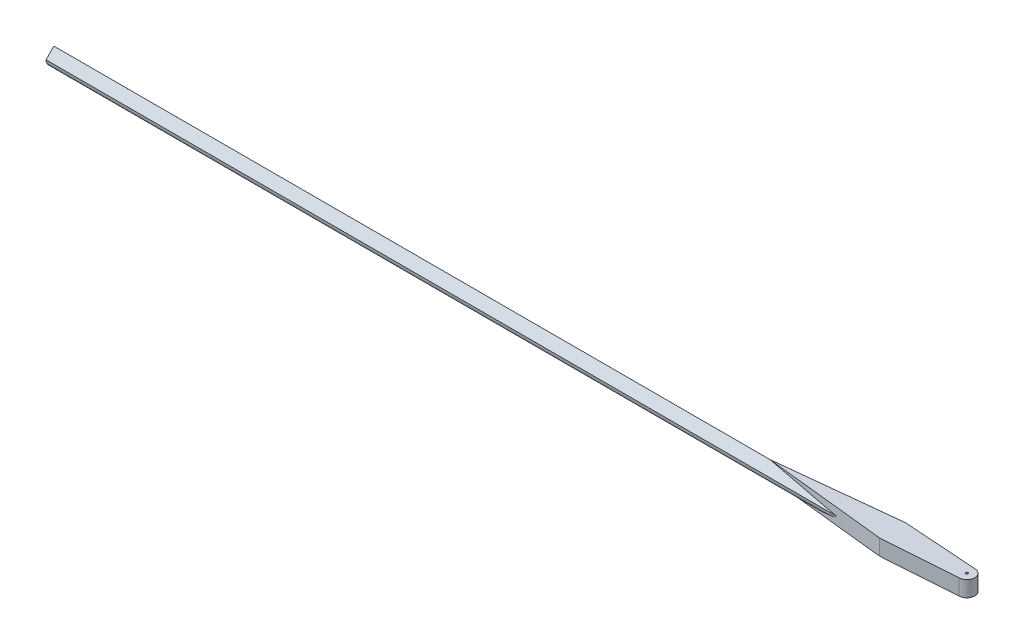
SolidWorks part; units mm, degrees
ref_plane "Front Plane" through (0, 0, 0) normal (0, 0, 1) x (1, 0, 0)
ref_plane "Top Plane" through (0, 0, 0) normal (0, 1, 0) x (1, 0, 0)
ref_plane "Right Plane" through (0, 0, 0) normal (1, 0, 0) x (0, 0, -1)
sketch "Sketch1" plane through (0, 0, 0) normal (0, 1, 0) x (1, 0, 0)
  line L0 (500, 10.0017) -> (561.4102, 16.5533)
  line L1 (-500, 10.0017) -> (500, 10.0017)
  line L2 (-500, 10.0017) -> (-500, -10.0017)
  line L3 (-500, -10.0017) -> (500, -10.0017)
  line L5 (-500, 10.0017) -> (500, -10.0017) construction
  line L6 (-500, -10.0017) -> (500, 10.0017) construction
  line L7 (561.4102, 16.5533) -> (655.434, 10.0017)
  line L9 (561.4102, -16.5533) -> (655.434, -10.0017)
  line L10 (500, -10.0017) -> (561.4102, -16.5533)
  arc A0 (655.434, 10.0017) -> (655.434, -10.0017) centre (655.434, 0) cw
  circle A1 centre (655.434, 0) radius 1.5
  point P0 (0, 0)
  dimension "D1" = 20.0034
  dimension "D2" = 1000
extrude "Boss-Extrude1" add sketch "Sketch1" along normal mid plane 20
chamfer "Chamfer1" distance 10 angle 45 2 edges at (0, 10, -10.0017) (0, 10, 10.0017)
fillet "Fillet1" radius 10 2 edges at (0, -10, 10.0017) (0, -10, -10.0017)
